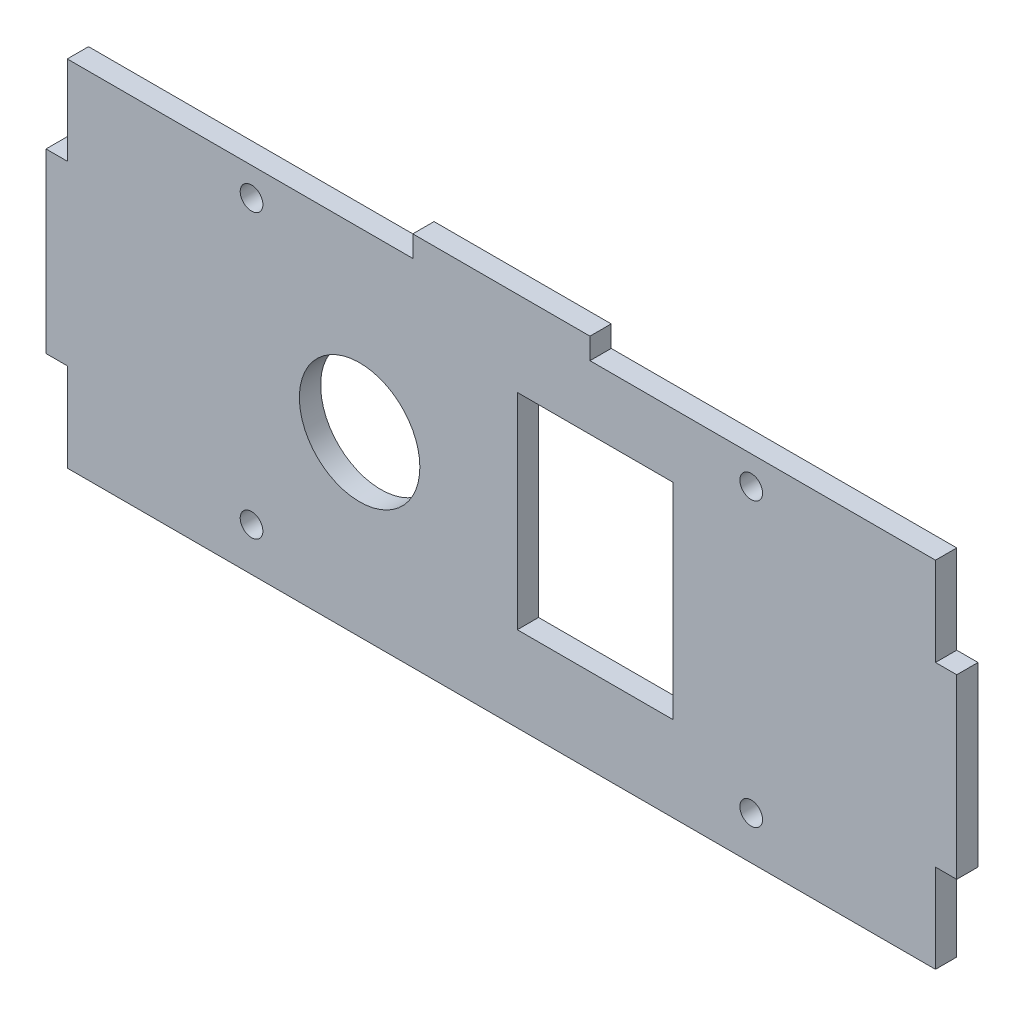
SolidWorks part; units mm, degrees
ref_plane "Plan de face" through (0, 0, 0) normal (0, 0, 1) x (1, 0, 0)
ref_plane "Plan de dessus" through (0, 0, 0) normal (0, 1, 0) x (1, 0, 0)
ref_plane "Plan de droite" through (0, 0, 0) normal (1, 0, 0) x (0, 0, -1)
sketch "Esquisse1" plane through (0, 0, 0) normal (0, 0, 1) x (1, 0, 0)
  line L28 (0, 45.0201) -> (0, -32.3311) construction
  line L29 (61.25, -25) -> (-61.25, -25)
  line L30 (61.25, -25) -> (61.25, -12.5)
  line L31 (61.25, 25) -> (29.85, 25)
  line L32 (-61.25, -25) -> (-61.25, -12.5)
  line L33 (61.25, -25) -> (-61.25, 25) construction
  line L34 (61.25, 25) -> (-61.25, -25) construction
  line L71 (61.25, 12.5) -> (64.25, 12.5)
  line L72 (-61.25, -12.5) -> (-64.25, -12.5)
  line L74 (-61.25, 12.5) -> (-64.25, 12.5)
  line L75 (-64.25, -12.5) -> (-64.25, 12.5)
  line L76 (64.25, -12.5) -> (64.25, 12.5)
  line L77 (61.25, -12.5) -> (64.25, -12.5)
  line L79 (-61.25, 12.5) -> (-61.25, 25)
  line L80 (61.25, 12.5) -> (61.25, 25)
  line L81 (26.65, 25) -> (12.5, 25)
  line L82 (-29.85, 25) -> (-61.25, 25)
  line L83 (-12.5, 25) -> (-26.65, 25)
  line L85 (-12.5, 25) -> (-12.5, 28)
  line L86 (-12.5, 28) -> (12.5, 28)
  line L87 (12.5, 25) -> (12.5, 28)
  line L88 (-29.85, 25) -> (-26.65, 25)
  line L89 (26.65, 25) -> (29.85, 25)
  point P0 (0, 0)
  point P44 (0, 28)
  dimension "D1" = 50
  dimension "D2" = 122.5
  dimension "D5" = 25
  dimension "D6" = 3
  dimension "D7" = 25
  dimension "D8" = 3
extrude "Boss.-Extru.1" add sketch "Esquisse1" along normal blind 3
sketch "Sketch1" plane through (0, 0, 0) normal (0, 0, -1) x (-1, 0, 0)
  circle A0 centre (35.25, 21) radius 1.6
extrude "Cut-Extrude1" cut sketch "Sketch1" against normal through all
sketch "Sketch2" plane through (0, 0, 0) normal (0, 0, -1) x (-1, 0, 0)
  circle A0 centre (-35.25, 21) radius 1.6
extrude "Cut-Extrude2" cut sketch "Sketch2" against normal through all
sketch "Sketch3" plane through (0, 0, 0) normal (0, 0, -1) x (-1, 0, 0)
  circle A0 centre (35.25, -18.9) radius 1.6
  circle A1 centre (-35.25, -18.9) radius 1.6
extrude "Cut-Extrude3" cut sketch "Sketch3" against normal through all
sketch "Sketch4" plane through (0, 0, 3) normal (0, 0, 1) x (1, 0, 0)
  line L1 (2.25, 16) -> (24.25, 16)
  line L2 (2.25, 16) -> (2.25, -13)
  line L3 (2.25, -13) -> (24.25, -13)
  line L4 (24.25, 16) -> (24.25, -13)
extrude "Cut-Extrude4" cut sketch "Sketch4" against normal through all
sketch "Sketch5" plane through (0, 0, 3) normal (0, 0, 1) x (1, 0, 0)
  circle A0 centre (-20, 0) radius 8.5
  dimension "D1" = 17
  dimension "D2" = 20
extrude "Cut-Extrude5" cut sketch "Sketch5" against normal through all
